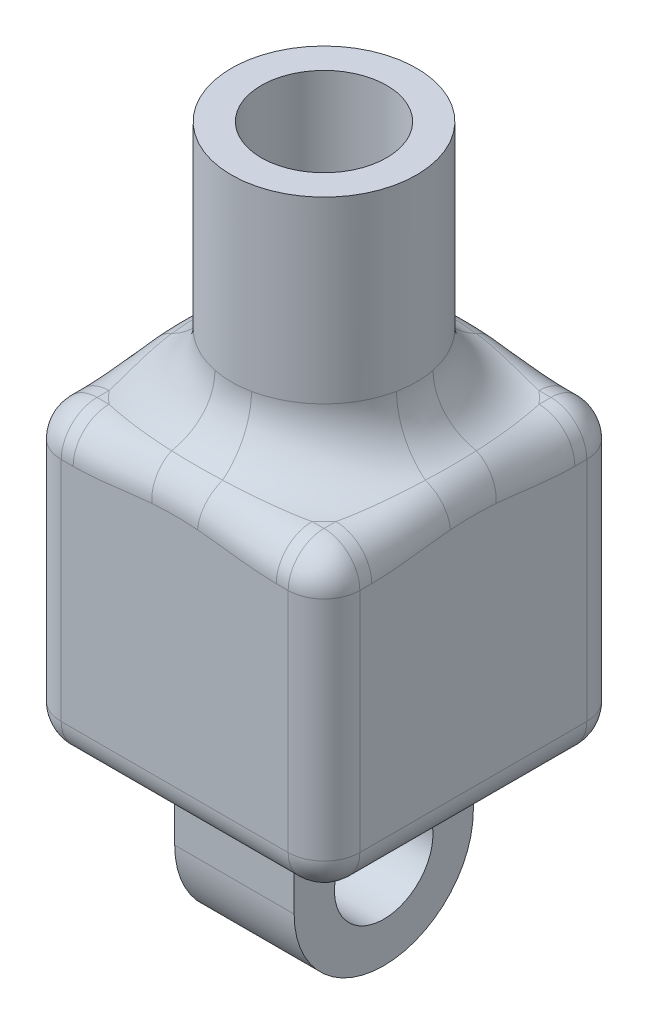
SolidWorks part; units mm, degrees
ref_plane "Front Plane" through (0, 0, 0) normal (0, 0, 1) x (1, 0, 0)
ref_plane "Top Plane" through (0, 0, 0) normal (0, 1, 0) x (1, 0, 0)
ref_plane "Right Plane" through (0, 0, 0) normal (1, 0, 0) x (0, 0, -1)
sketch "Sketch6" plane through (0, 0, 0) normal (0, 0, 1) x (1, 0, 0)
  line L1 (-25, 25) -> (25, 25)
  line L2 (-25, 25) -> (-25, -25)
  line L3 (-25, -25) -> (25, -25)
  line L4 (25, 25) -> (25, -25)
  point P4 (0, 25)
  point P6 (-25, 0)
  dimension "D1" = 50
  dimension "D2" = 50
extrude "Boss-Extrude1" add sketch "Sketch6" along normal mid plane 50
sketch "Sketch7" plane through (0, 25, 0) normal (0, 1, 0) x (1, 0, 0)
  line L1 (25, 25) -> (-25, 25) construction
  line L2 (-25, -25) -> (-25, 25) construction
  circle A0 centre (0, 0) radius 10.5
  circle A1 centre (0, 0) radius 15.5
  point P3 (0, 0)
  point P6 (0, 25)
  point P9 (-25, 0)
  dimension "D1" = 21
  dimension "D2" = 5
extrude "Boss-Extrude2" add sketch "Sketch7" along normal blind 40
sketch "Sketch9" plane through (0, 0, 0) normal (1, 0, 0) x (0, 0, -1)
  line L0 (-15, 0) -> (15, 0)
  line L1 (-25, -25) -> (25, -25) construction
  line L2 (-15, -25) -> (15, -25)
  line L3 (-15, -25) -> (-15, -37.4269)
  line L5 (15, -25) -> (15, -37.4269)
  arc A0 (-15, -37.4269) -> (15, -37.4269) centre (0, -37.4269) ccw
  circle A1 centre (0, -37.4269) radius 8.25
  point P4 (0, 0)
  dimension "D1" = 16.5
extrude "Boss-Extrude3" add sketch "Sketch9" along normal mid plane 20 separate body contours L3 A0 L5 L2
combine bodies "Combine2" operation type add bodies to combine 102 103
extrude "Cut-Extrude1" cut sketch "Sketch9<3>" against normal through all both and the other way through all contours A1
sketch "Sketch9<3>" plane through (0, 0, 0) normal (1, 0, 0) x (0, 0, -1) same geometry as "Sketch9"
fillet "Fillet2" radius 10 1 edges at (0, 25, -15.5)
fillet "Fillet3" radius 6 20 edges at (-15.0125, 25, 25) (0, 25, 25) (15.0125, 25, 25) (0, -25, 25) (-25, 25, -15.0125) (-25, 25, 0) (-25, 25, 15.0125) (-25, 0, 25) (-25, -25, 0) (0, -25, -25) (15.0125, 25, -25) (0, 25, -25) (-15.0125, 25, -25) (-25, 0, -25) (25, -25, 0) (25, 0, 25) (25, 25, 15.0125) (25, 25, 0) (25, 25, -15.0125) (25, 0, -25)
